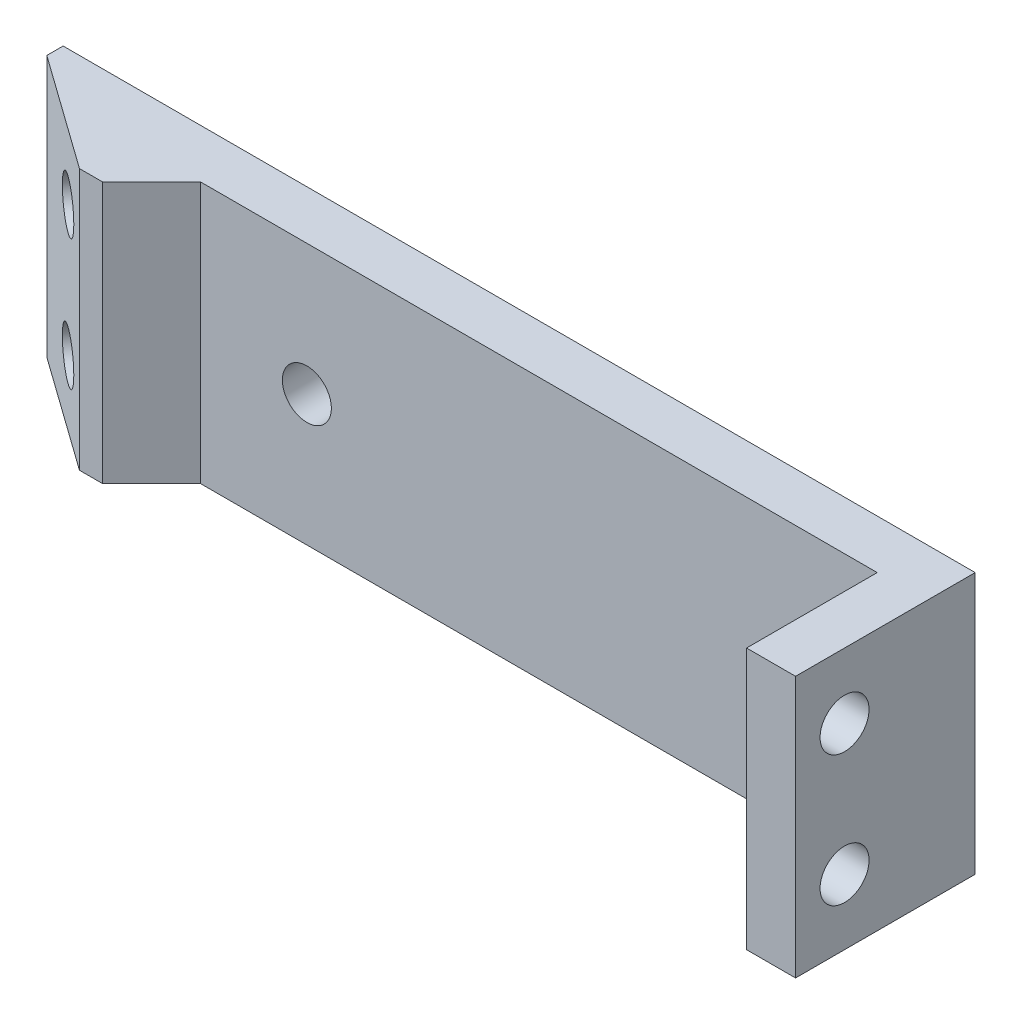
SolidWorks part; units mm, degrees
ref_plane "Front Plane" through (0, 0, 0) normal (0, 0, 1) x (1, 0, 0)
ref_plane "Top Plane" through (0, 0, 0) normal (0, 1, 0) x (1, 0, 0)
ref_plane "Right Plane" through (0, 0, 0) normal (1, 0, 0) x (0, 0, -1)
sketch "Sketch1" plane through (0, 0, 0) normal (0, 0, 1) x (1, 0, 0)
  line L1 (-27.925, -8) -> (27.925, -8)
  line L2 (-27.925, -8) -> (-27.925, 8)
  line L3 (-27.925, 8) -> (27.925, 8)
  line L4 (27.925, -8) -> (27.925, 8)
  line L5 (-27.925, -8) -> (27.925, 8) construction
  line L6 (-27.925, 8) -> (27.925, -8) construction
  point P0 (0, 0)
  dimension "D1" = 55.85
  dimension "D2" = 16
extrude "Boss-Extrude1" add sketch "Sketch1" along normal blind 3
sketch "Sketch2" plane through (0, 0, 3) normal (0, 0, 1) x (1, 0, 0)
  line L0 (-27.925, -8) -> (27.925, -8) construction
  line L1 (-27.925, 8) -> (-19.525, 8)
  line L2 (-27.925, 8) -> (-27.925, -8)
  line L3 (-27.925, -8) -> (-19.525, -8)
  line L4 (-19.525, 8) -> (-19.525, -8)
  dimension "D1" = 8.4
extrude "Boss-Extrude2" add sketch "Sketch2" along normal blind 3
chamfer "Chamfer1" distance 5 distance2 7 1 edges at (-27.925, 0, 6) first distance on face at (-27.925, 0, 3)
sketch "Sketch3" plane through (-9.9071, 0, 13.8699) normal (-0.5812, 0, 0.8137) x (0.8137, 0, 0.5812)
  line L0 (-22.1423, 8) -> (-13.5399, 8) construction
  line L1 (-13.5399, -8) -> (-22.1423, -8) construction
  line L2 (-13.5399, 8) -> (-13.5399, -8) construction
  circle A0 centre (-16.5399, 4) radius 1.5
  circle A1 centre (-16.5399, -4) radius 1.5
  dimension "D1" = 3
  dimension "D2" = 3
  dimension "D3" = 4
  dimension "D4" = 4
  dimension "D6" = 3
  dimension "D5" = 3
extrude "Cut-Extrude1" cut sketch "Sketch3" against normal blind 3
chamfer "Chamfer2" distance 3 angle 45 1 edges at (-19.525, 0, 3)
sketch "Sketch4" plane through (-9.9071, 0, 13.8699) normal (-0.5812, 0, 0.8137) x (0.8137, 0, 0.5812)
  line L1 (-13.3645, 4) -> (-14.9522, 6.75)
  line L2 (-14.9522, 6.75) -> (-18.1277, 6.75)
  line L3 (-18.1277, 6.75) -> (-19.7154, 4)
  line L4 (-19.7154, 4) -> (-18.1277, 1.25)
  line L5 (-18.1277, 1.25) -> (-14.9522, 1.25)
  line L6 (-14.9522, 1.25) -> (-13.3645, 4)
  line L7 (-13.3645, -4) -> (-14.9522, -1.25)
  line L8 (-14.9522, -1.25) -> (-18.1277, -1.25)
  line L9 (-18.1277, -1.25) -> (-19.7154, -4)
  line L10 (-19.7154, -4) -> (-18.1277, -6.75)
  line L11 (-18.1277, -6.75) -> (-14.9522, -6.75)
  line L12 (-14.9522, -6.75) -> (-13.3645, -4)
  circle A0 centre (-16.5399, 4) radius 2.75 construction
  circle A1 centre (-16.5399, -4) radius 2.75 construction
  dimension "D1" = 5.5
  dimension "D2" = 5.5
extrude "Cut-Extrude2" cut sketch "Sketch4" against normal blind 8 from offset 3 offset against normal yes
sketch "Sketch5" plane through (0, 0, 3) normal (0, 0, 1) x (1, 0, 0)
  line L0 (-16.525, -8) -> (27.925, -8) construction
  line L1 (27.925, 8) -> (24.925, 8)
  line L2 (27.925, 8) -> (27.925, -8)
  line L3 (27.925, -8) -> (24.925, -8)
  line L4 (24.925, 8) -> (24.925, -8)
  dimension "D1" = 3
extrude "Boss-Extrude3" add sketch "Sketch5" along normal blind 8
sketch "Sketch6" plane through (27.925, 0, 0) normal (1, 0, 0) x (0, 0, -1)
  line L0 (-11, -8) -> (-11, 8) construction
  line L1 (-11, 8) -> (0, 8) construction
  line L2 (-11, -8) -> (0, -8) construction
  circle A0 centre (-8, 4) radius 1.5
  circle A1 centre (-8, -4) radius 1.5
  dimension "D1" = 3
  dimension "D2" = 3
  dimension "D3" = 3
  dimension "D4" = 3
  dimension "D5" = 4
  dimension "D6" = 4
extrude "Cut-Extrude3" cut sketch "Sketch6" against normal blind 8
sketch "Sketch7" plane through (0, 0, 0) normal (0, 0, -1) x (-1, 0, 0)
  circle A0 centre (10, 0) radius 1.5
  dimension "D1" = 3
  dimension "D2" = 10
extrude "Cut-Extrude4" cut sketch "Sketch7" against normal blind 10
